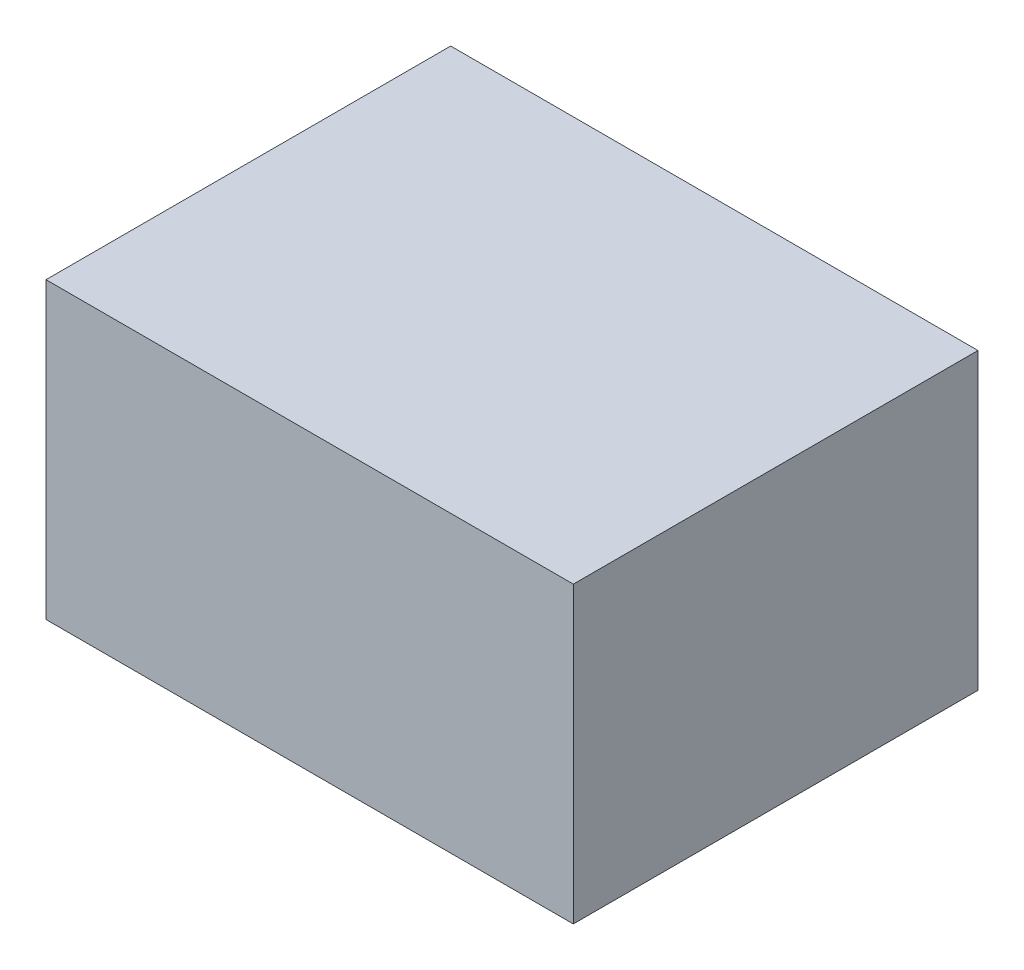
SolidWorks part; units mm, degrees
ref_plane "Front Plane" through (0, 0, 0) normal (0, 0, 1) x (1, 0, 0)
ref_plane "Top Plane" through (0, 0, 0) normal (0, 1, 0) x (1, 0, 0)
ref_plane "Right Plane" through (0, 0, 0) normal (1, 0, 0) x (0, 0, -1)
sketch "Case Sketch" plane through (0, 0, 0) normal (0, 1, 0) x (1, 0, 0)
  line L0 (-21.5, 16.5) -> (21.5, 16.5)
  line L1 (21.5, 16.5) -> (21.5, -16.5)
  line L2 (21.5, -16.5) -> (-21.5, -16.5)
  line L3 (-21.5, -16.5) -> (-21.5, 16.5)
extrude "Case" add sketch "Case Sketch" along normal blind 24 from offset 68.57
ref_axis "Engine Axis" through (23.65, 0, 0) along (-1, 0, 0)
